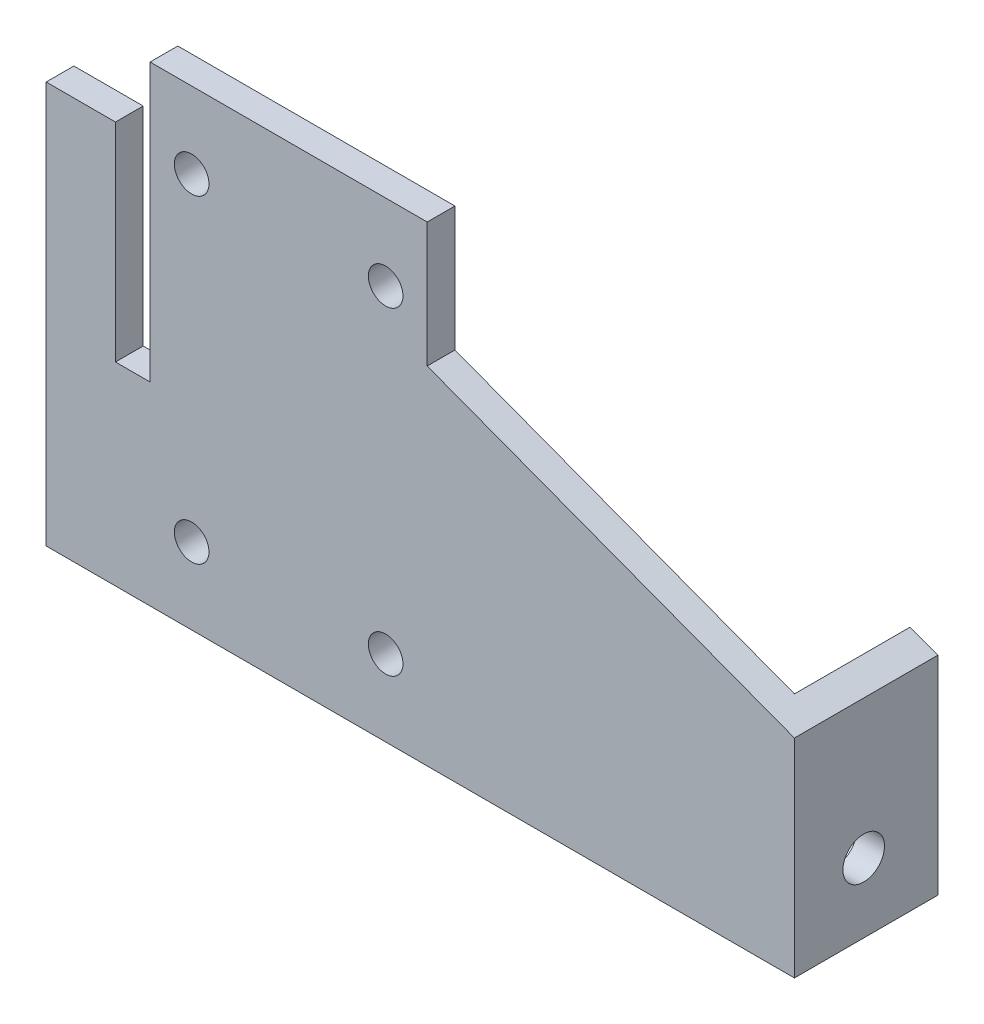
SolidWorks part; units mm, degrees
ref_plane "Спереди" through (0, 0, 0) normal (0, 0, 1) x (1, 0, 0)
ref_plane "Сверху" through (0, 0, 0) normal (0, 1, 0) x (1, 0, 0)
ref_plane "Справа" through (0, 0, 0) normal (1, 0, 0) x (0, 0, -1)
sketch "Эскиз1" plane through (0, 0, 0) normal (0, 0, 1) x (1, 0, 0)
  line L0 (35, 68) -> (35, 0) construction
  line L1 (0, 0) -> (108, 0)
  line L2 (0, 0) -> (0, 68)
  line L3 (0, 68) -> (55, 68)
  line L4 (108, 0) -> (108, 30)
  line L5 (21, 68) -> (21, 0) construction
  line L6 (55, 68) -> (55, 50)
  line L8 (49, 68) -> (49, 0) construction
  line L10 (108, 30) -> (55, 50)
  circle A0 centre (21, 57) radius 2.5
  circle A1 centre (49, 57) radius 2.5
  circle A2 centre (21, 11) radius 2.5
  circle A3 centre (49, 11) radius 2.5
  dimension "D8" = 5
  dimension "D9" = 5
  dimension "D10" = 5
  dimension "D11" = 5
  dimension "D1" = 108
  dimension "D2" = 68
  dimension "D3" = 53
  dimension "D4" = 30
  dimension "D5" = 20
  dimension "D6" = 14
  dimension "D7" = 14
  dimension "D12" = 46
  dimension "D13" = 46
  dimension "D14" = 11
  dimension "D15" = 11
  dimension "D16" = 20
extrude "Бобышка-Вытянуть1" add sketch "Эскиз1" along normal blind 4
sketch "Эскиз2" plane through (0, 0, 4) normal (0, 0, 1) x (1, 0, 0)
  line L1 (108, 0) -> (104, 0)
  line L2 (0, 0) -> (108, 0) construction
  line L3 (104, 0) -> (104, 31.5094)
  line L4 (108, 30) -> (55, 50) construction
  line L5 (104, 31.5094) -> (108, 30)
  line L6 (108, 30) -> (108, 0)
  dimension "D1" = 4
extrude "Бобышка-Вытянуть2" add sketch "Эскиз2" against normal blind 20.7
sketch "Эскиз3" plane through (108, 0, 0) normal (1, 0, 0) x (0, 0, -1)
  line L2 (-4, 0) -> (-4, 30) construction
  line L4 (-4, 0) -> (16.7, 0) construction
  circle A0 centre (6, 10) radius 3
  dimension "D1" = 6
  dimension "D2" = 10
  dimension "D3" = 10
extrude "Вырез-Вытянуть1" cut sketch "Эскиз3" against normal blind 6.7
sketch "Эскиз4" plane through (0, 0, 0) normal (0, 0, -1) x (-1, 0, 0)
  line L1 (0, 68) -> (-15, 68)
  line L2 (0, 68) -> (0, 58)
  line L3 (0, 58) -> (-10, 58)
  line L4 (-15, 68) -> (-15, 48)
  line L6 (-15, 48) -> (-15, 28)
  line L7 (-15, 28) -> (-10, 28)
  line L8 (-10, 58) -> (-10, 28)
  dimension "D1" = 10
  dimension "D2" = 10
  dimension "D3" = 40
  dimension "D4" = 5
extrude "Вырез-Вытянуть2" cut sketch "Эскиз4" against normal blind 10
